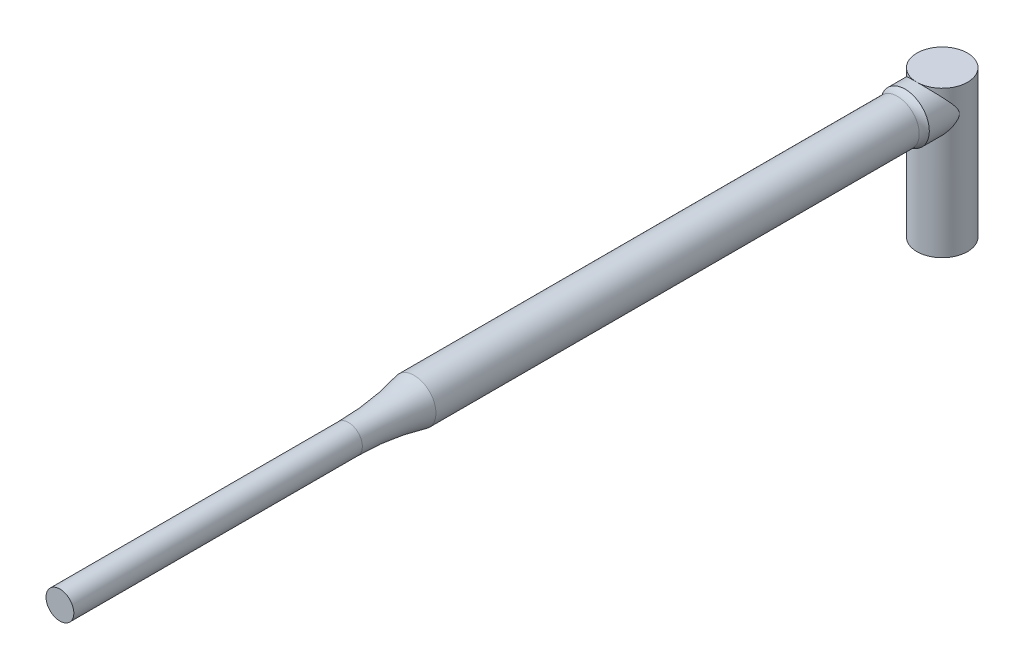
SolidWorks part; units mm, degrees
ref_plane "Front Plane" through (0, 0, 0) normal (0, 0, 1) x (1, 0, 0)
ref_plane "Top Plane" through (0, 0, 0) normal (0, 1, 0) x (1, 0, 0)
ref_plane "Right Plane" through (0, 0, 0) normal (1, 0, 0) x (0, 0, -1)
sketch "Sketch1" plane through (0, 0, 0) normal (0, 1, 0) x (1, 0, 0)
  circle A0 centre (0, 0) radius 5
  dimension "D1" = 10
extrude "Boss-Extrude1" add sketch "Sketch1" along normal blind 29
sketch "Sketch2" plane through (0, 0, 0) normal (0, 0, 1) x (1, 0, 0)
  line L0 (0, 24.2) -> (0, 0) construction
  line L1 (5, 29) -> (-5, 29) construction
  circle A0 centre (0, 24.2) radius 4.8
  dimension "D1" = 9.6
extrude "Boss-Extrude2" add sketch "Sketch2" along normal blind 7.35
sketch "Sketch3" plane through (0, 0, 7.35) normal (0, 0, 1) x (1, 0, 0)
  line L0 (0, 29) -> (0, 19.4) construction
  circle A0 centre (0, 24.2) radius 4.8 construction
  circle A1 centre (0, 24.2) radius 4.305
  dimension "D1" = 8.61
extrude "Boss-Extrude3" add sketch "Sketch3" along normal blind 97
sketch "Sketch4" plane through (0, 0, 104.35) normal (0, 0, 1) x (1, 0, 0)
  line L0 (0, 28.505) -> (0, 19.895) construction
  circle A0 centre (0, 24.2) radius 4.305 construction
  circle A1 centre (0, 24.2) radius 2.75
  dimension "D1" = 5.5
extrude "Boss-Extrude4" add sketch "Sketch4" along normal blind 70
fillet "Fillet1" radius 55 1 edges at (2.75, 24.2, 104.35)
fillet "Fillet2" radius 2.5 1 edges at (4.305, 24.2, 7.35)
